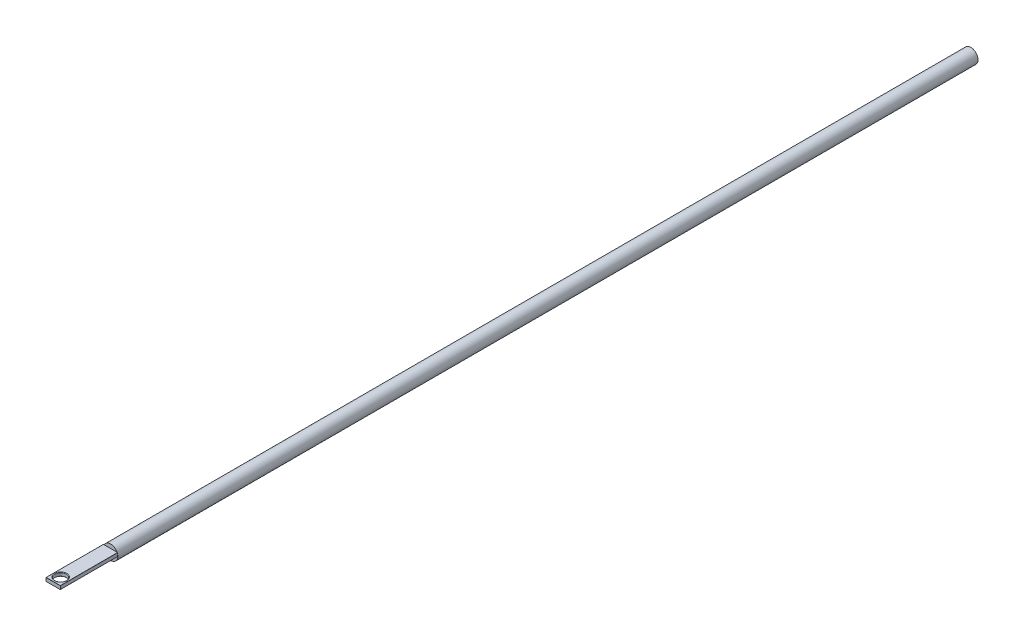
SolidWorks part; units mm, degrees
ref_plane "Ön Düzlem" through (0, 0, 0) normal (0, 0, 1) x (1, 0, 0)
ref_plane "Üst Düzlem" through (0, 0, 0) normal (0, 1, 0) x (1, 0, 0)
ref_plane "Sağ Düzlem" through (0, 0, 0) normal (1, 0, 0) x (0, 0, -1)
sketch "Sketch1" plane through (0, 0, 0) normal (0, 0, 1) x (1, 0, 0)
  circle A0 centre (0, 0) radius 6.25
  dimension "D1" = 12.5
extrude "Boss-Extrude1" add sketch "Sketch1" along normal blind 750
sketch "Sketch9" plane through (0, 0, 0) normal (0, 1, 0) x (1, 0, 0)
  line L1 (-6.1863, -750.1979) -> (6.3137, -750.1979)
  line L2 (-6.1863, -750.1979) -> (-6.1863, -800.1979)
  line L3 (-6.1863, -800.1979) -> (6.3137, -800.1979)
  line L4 (6.3137, -750.1979) -> (6.3137, -800.1979)
  line L5 (-6.1863, -750.1979) -> (6.3137, -800.1979) construction
  line L6 (-6.1863, -800.1979) -> (6.3137, -750.1979) construction
  circle A0 centre (-0.0889, -793.4973) radius 5
  point P4 (0.0637, -775.1979)
  dimension "D3" = 10
  dimension "D1" = 50
  dimension "D2" = 12.5
extrude "Boss-Extrude5" add sketch "Sketch9" along normal blind 3 separate body contours A0 | L2 L1 L4 L3 region at (-0.0889, 0, 793.4973)
fillet "Fillet3" radius 0.1 6 edges at (-0.0889, 0, 798.4973) (0.0637, 3, 800.1979) (6.3137, 0, 775.1979) (-6.1863, 0, 775.1979) (6.3137, 3, 775.1979) (-6.1863, 3, 775.1979)
fillet "Fillet5" radius 0.5 1 edges at (-0.0889, 3, 798.4973)
